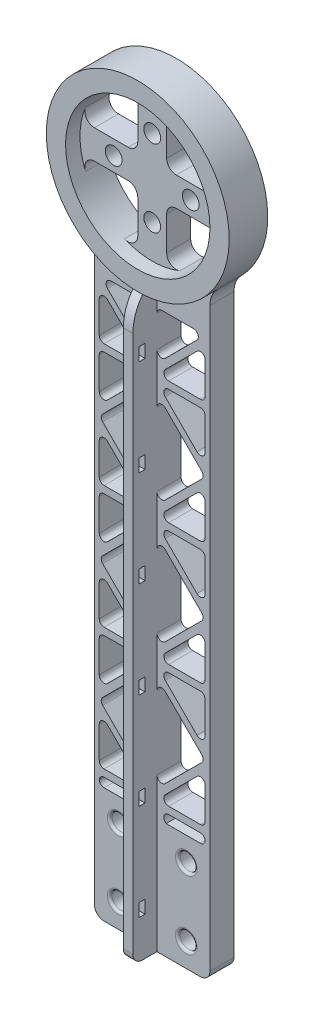
SolidWorks part; units mm, degrees
material "ABS"
ref_plane "Front Plane" through (0, 0, 0) normal (0, 0, 1) x (1, 0, 0)
ref_plane "Top Plane" through (0, 0, 0) normal (0, 1, 0) x (1, 0, 0)
ref_plane "Right Plane" through (0, 0, 0) normal (1, 0, 0) x (0, 0, -1)
sketch "Sketch2" plane through (0, 0, 0) normal (0, 0, 1) x (1, 0, 0)
  line L0 (0, 15) -> (0, -15) construction
  line L1 (-15, 0) -> (15, 0) construction
  line L2 (-3, 14.6969) -> (-3, 3)
  line L3 (-3, 3) -> (-14.6969, 3)
  line L4 (-14.6969, -3) -> (-3, -3)
  line L5 (-3, -3) -> (-3, -14.6969)
  line L6 (3, 14.6969) -> (3, 3)
  line L7 (3, 3) -> (14.6969, 3)
  line L8 (3, -14.6969) -> (3, -3)
  line L9 (3, -3) -> (14.6969, -3)
  line L10 (-12, -14.7309) -> (-12, -114.7309)
  line L11 (12, -14.7309) -> (12, -114.7309)
  line L12 (12, -114.7309) -> (-12, -114.7309)
  circle A0 centre (0, 0) radius 19
  circle A1 centre (0, 0) radius 15
  arc A2 (3, -14.6969) -> (14.6969, -3) centre (0, 0) ccw
  arc A3 (3, 14.6969) -> (14.6969, 3) centre (0, 0) cw
  arc A4 (-14.6969, 3) -> (-3, 14.6969) centre (0, 0) cw
  arc A5 (-14.6969, -3) -> (-3, -14.6969) centre (0, 0) ccw
  arc A6 (-12, -14.7309) -> (12, -14.7309) centre (0, 0) ccw
  dimension "D1" = 30
  dimension "D2" = 4
  dimension "D3" = 3
  dimension "D4" = 3
  dimension "D5" = 3
  dimension "D6" = 3
  dimension "D7" = 3
  dimension "D8" = 3
  dimension "D9" = 3
  dimension "D10" = 3
  dimension "D11" = 3
  dimension "D12" = 3
  dimension "D13" = 100
extrude "Boss-Extrude2" add sketch "Sketch2" along normal blind 8 contours A0 A1 L5 region at (-7.9241, 16.6756, 0)
extrude "Boss-Extrude3" add sketch "Sketch2<6>" along normal blind 5 contours L6 A1 L2 L3 L4 L5 L8 L9 L7 region at (0, 0, 0)
sketch "Sketch2<6>" plane through (0, 0, 0) normal (0, 0, 1) x (1, 0, 0) same geometry as "Sketch2"
fillet "Fillet1" radius 2 12 edges at (-3, 3, 2.5) (3, 3, 2.5) (3, -3, 2.5) (-3, -3, 2.5) (-3, -14.6969, 2.5) (3, -14.6969, 2.5) (14.6969, -3, 2.5) (14.6969, 3, 2.5) (3, 14.6969, 2.5) (-3, 14.6969, 2.5) (-14.6969, -3, 2.5) (-14.6969, 3, 2.5)
sketch "Sketch6" plane through (0, 0, 0) normal (0, 0, 1) x (1, 0, 0)
  line L0 (0, 0) -> (0, 8.3) construction
  line L1 (0, 0) -> (0, -8.3) construction
  line L2 (0, 0) -> (8.35, 0) construction
  line L3 (0, 0) -> (-8.35, 0) construction
  circle A0 centre (8, 0) radius 1.75
  circle A1 centre (0, 8) radius 1.75
  circle A2 centre (-8, 0) radius 1.75
  circle A3 centre (0, -8) radius 1.75
  dimension "D1" = 3.5
  dimension "D2" = 8
  dimension "D3" = 8
  dimension "D4" = 8
  dimension "D5" = 8
extrude "Cut-Extrude2" cut sketch "Sketch6" along normal up to surface (5 mm away) up to face at (0, 0, 5)
extrude "Boss-Extrude4" add sketch "Sketch2<9>" along normal up to surface (5 mm away) contours A0 L10 L12 L11 region at (0, -66.1813, 0) up to face at (9.75, 0, 5)
sketch "Sketch2<9>" plane through (0, 0, 0) normal (0, 0, 1) x (1, 0, 0) same geometry as "Sketch2"
fillet "Fillet2" radius 5 2 edges at (12, -14.7309, 2.5) (-12, -14.7309, 2.5)
sketch "Sketch9" plane through (0, 0, 5) normal (0, 0, 1) x (1, 0, 0)
  line L0 (0, -19) -> (0, -114.7309) construction
  line L1 (12, -114.7309) -> (-12, -114.7309) construction
  line L2 (-11, -203.3442) -> (-11, -213.3442)
  line L3 (-11, -213.3442) -> (-1, -213.3442)
  line L4 (-1, -213.3442) -> (-11, -203.3442)
  line L5 (-11, -201.3442) -> (-1, -211.3442)
  line L6 (-1, -211.3442) -> (-1, -191.3442)
  line L7 (-1, -201.3442) -> (-11, -201.3442)
  line L8 (-11, -189.3442) -> (-1, -189.3442)
  line L9 (-11, -199.3442) -> (-11, -189.3442)
  line L10 (-1, -189.3442) -> (-11, -199.3442)
  line L11 (-11, -201.3442) -> (-1, -191.3442)
  line L12 (-11, -163.8442) -> (-1, -163.8442)
  line L13 (-1, -163.8442) -> (-11, -173.8442)
  line L14 (-11, -173.8442) -> (-11, -163.8442)
  line L15 (-11, -175.8442) -> (-1, -185.8442)
  line L16 (-1, -185.8442) -> (-1, -165.8442)
  line L17 (-11, -175.8442) -> (-1, -165.8442)
  line L18 (-1, -187.8442) -> (-11, -177.8442)
  line L19 (-11, -177.8442) -> (-11, -187.8442)
  line L20 (-11, -187.8442) -> (-1, -187.8442)
  line L21 (-11, -138.3442) -> (-1, -138.3442)
  line L22 (-1, -138.3442) -> (-11, -148.3442)
  line L23 (-11, -148.3442) -> (-11, -138.3442)
  line L24 (-11, -150.3442) -> (-1, -160.3442)
  line L25 (-1, -160.3442) -> (-1, -140.3442)
  line L26 (-11, -150.3442) -> (-1, -140.3442)
  line L27 (-1, -162.3442) -> (-11, -152.3442)
  line L28 (-11, -152.3442) -> (-11, -162.3442)
  line L29 (-11, -162.3442) -> (-1, -162.3442)
  line L30 (-11, -112.8442) -> (-1, -112.8442)
  line L31 (-1, -112.8442) -> (-11, -122.8442)
  line L32 (-11, -122.8442) -> (-11, -112.8442)
  line L33 (-11, -124.8442) -> (-1, -134.8442)
  line L34 (-1, -134.8442) -> (-1, -114.8442)
  line L35 (-11, -124.8442) -> (-1, -114.8442)
  line L36 (-1, -136.8442) -> (-11, -126.8442)
  line L37 (-11, -126.8442) -> (-11, -136.8442)
  line L38 (-11, -136.8442) -> (-1, -136.8442)
  line L39 (-11, -87.3442) -> (-1, -87.3442)
  line L40 (-1, -87.3442) -> (-11, -97.3442)
  line L41 (-11, -97.3442) -> (-11, -87.3442)
  line L42 (-11, -99.3442) -> (-1, -109.3442)
  line L43 (-1, -109.3442) -> (-1, -89.3442)
  line L44 (-11, -99.3442) -> (-1, -89.3442)
  line L45 (-1, -111.3442) -> (-11, -101.3442)
  line L46 (-11, -101.3442) -> (-11, -111.3442)
  line L47 (-11, -111.3442) -> (-1, -111.3442)
  line L48 (-11, -61.8442) -> (-1, -61.8442)
  line L49 (-1, -61.8442) -> (-11, -71.8442)
  line L50 (-11, -71.8442) -> (-11, -61.8442)
  line L51 (-11, -73.8442) -> (-1, -83.8442)
  line L52 (-1, -83.8442) -> (-1, -63.8442)
  line L53 (-11, -73.8442) -> (-1, -63.8442)
  line L54 (-1, -85.8442) -> (-11, -75.8442)
  line L55 (-11, -75.8442) -> (-11, -85.8442)
  line L56 (-11, -85.8442) -> (-1, -85.8442)
  line L57 (-11, -36.3442) -> (-1, -36.3442)
  line L58 (-1, -36.3442) -> (-11, -46.3442)
  line L59 (-11, -46.3442) -> (-11, -36.3442)
  line L60 (-11, -48.3442) -> (-1, -58.3442)
  line L61 (-1, -58.3442) -> (-1, -38.3442)
  line L62 (-11, -48.3442) -> (-1, -38.3442)
  line L63 (-1, -60.3442) -> (-11, -50.3442)
  line L64 (-11, -50.3442) -> (-11, -60.3442)
  line L65 (-11, -60.3442) -> (-1, -60.3442)
  line L69 (-11, -22.8442) -> (-1, -32.8442)
  line L70 (-1, -32.8442) -> (-1, -22.8442)
  line L72 (-1, -34.8442) -> (-11, -24.8442)
  line L73 (-11, -24.8442) -> (-11, -34.8442)
  line L74 (-11, -34.8442) -> (-1, -34.8442)
  line L75 (11, -22.8442) -> (1, -22.8442)
  line L76 (-11, -22.8442) -> (-1, -22.8442)
  line L77 (1, -32.8442) -> (1, -22.8442)
  line L78 (-1, -10.8442) -> (-11, -20.8442)
  line L79 (-11, -16.8895) -> (-11, -10.8442)
  line L80 (-11, -10.8442) -> (-1, -10.8442)
  line L81 (-11, -22.8442) -> (-2.3104, -14.1546)
  line L82 (11, -22.8442) -> (1, -32.8442)
  line L83 (11, -34.8442) -> (1, -34.8442)
  line L84 (11, -24.8442) -> (11, -34.8442)
  line L85 (1, -34.8442) -> (11, -24.8442)
  line L86 (11, -46.3442) -> (11, -36.3442)
  line L87 (1, -36.3442) -> (11, -46.3442)
  line L88 (11, -36.3442) -> (1, -36.3442)
  line L89 (11, -48.3442) -> (1, -38.3442)
  line L90 (1, -58.3442) -> (1, -38.3442)
  line L91 (11, -48.3442) -> (1, -58.3442)
  line L92 (11, -60.3442) -> (1, -60.3442)
  line L93 (11, -50.3442) -> (11, -60.3442)
  line L94 (1, -60.3442) -> (11, -50.3442)
  line L95 (11, -71.8442) -> (11, -61.8442)
  line L96 (1, -61.8442) -> (11, -71.8442)
  line L97 (11, -61.8442) -> (1, -61.8442)
  line L98 (11, -73.8442) -> (1, -63.8442)
  line L99 (1, -83.8442) -> (1, -63.8442)
  line L100 (11, -73.8442) -> (1, -83.8442)
  line L101 (11, -85.8442) -> (1, -85.8442)
  line L102 (11, -75.8442) -> (11, -85.8442)
  line L103 (1, -85.8442) -> (11, -75.8442)
  line L104 (11, -97.3442) -> (11, -87.3442)
  line L105 (1, -87.3442) -> (11, -97.3442)
  line L106 (11, -87.3442) -> (1, -87.3442)
  line L107 (11, -99.3442) -> (1, -89.3442)
  line L108 (1, -109.3442) -> (1, -89.3442)
  line L109 (11, -99.3442) -> (1, -109.3442)
  line L110 (11, -111.3442) -> (1, -111.3442)
  line L111 (11, -101.3442) -> (11, -111.3442)
  line L112 (1, -111.3442) -> (11, -101.3442)
  line L113 (11, -122.8442) -> (11, -112.8442)
  line L114 (1, -112.8442) -> (11, -122.8442)
  line L115 (11, -112.8442) -> (1, -112.8442)
  line L116 (11, -124.8442) -> (1, -114.8442)
  line L117 (1, -134.8442) -> (1, -114.8442)
  line L118 (11, -124.8442) -> (1, -134.8442)
  line L119 (11, -136.8442) -> (1, -136.8442)
  line L120 (11, -126.8442) -> (11, -136.8442)
  line L121 (1, -136.8442) -> (11, -126.8442)
  line L122 (11, -148.3442) -> (11, -138.3442)
  line L123 (1, -138.3442) -> (11, -148.3442)
  line L124 (11, -138.3442) -> (1, -138.3442)
  line L125 (11, -150.3442) -> (1, -140.3442)
  line L126 (1, -160.3442) -> (1, -140.3442)
  line L127 (11, -150.3442) -> (1, -160.3442)
  line L128 (11, -162.3442) -> (1, -162.3442)
  line L129 (11, -152.3442) -> (11, -162.3442)
  line L130 (1, -162.3442) -> (11, -152.3442)
  line L131 (1, -163.8442) -> (11, -173.8442)
  line L132 (11, -173.8442) -> (11, -163.8442)
  line L133 (11, -163.8442) -> (1, -163.8442)
  line L134 (11, -175.8442) -> (1, -165.8442)
  line L135 (1, -185.8442) -> (1, -165.8442)
  line L136 (11, -175.8442) -> (1, -185.8442)
  line L137 (11, -177.8442) -> (11, -187.8442)
  line L138 (11, -187.8442) -> (1, -187.8442)
  line L139 (1, -187.8442) -> (11, -177.8442)
  line L140 (11, -199.3442) -> (11, -189.3442)
  line L141 (1, -189.3442) -> (11, -199.3442)
  line L142 (11, -189.3442) -> (1, -189.3442)
  line L143 (11, -201.3442) -> (1, -191.3442)
  line L144 (1, -211.3442) -> (1, -191.3442)
  line L145 (11, -201.3442) -> (1, -211.3442)
  line L146 (11, -213.3442) -> (1, -213.3442)
  line L147 (11, -203.3442) -> (11, -213.3442)
  line L148 (1, -213.3442) -> (11, -203.3442)
  arc A0 (-13.4583, -13.4117) -> (13.4583, -13.4117) centre (0, 0) ccw construction
  dimension "D1" = 10
  dimension "D2" = 10
  dimension "D3" = 10
  dimension "D4" = 10
  dimension "D5" = 1
  dimension "D6" = 2
  dimension "D7" = 8
extrude "Cut-Extrude4" cut sketch "Sketch9" against normal up to surface (5 mm away) contours L11 L7 L6 | L6 L7 L5 | L7 L5 L6 | L69 L70 L76 | L72 L73 L74 | L75 L77 L82 | L83 L85 L84 | L57 L58 L59 | L60 L61 L62 | L63 L64 L65 | L86 L88 L87 | L89 L90 L91 | L92 L94 L93 | L48 L49 L50 | L51 L52 L53 | L95 L97 L96 | L98 L99 L100 | L54 L55 L56 | L101 L103 L102 | L39 L40 L41 | L104 L106 L105 | L42 L43 L44 | L107 L108 L109 | L110 L112 L111 | L45 L46 L47 | L30 L31 L32 | L113 L115 L114 | L33 L34 L35 | L116 L117 L118 | L36 L37 L38 | L21 L22 L23 | L119 L121 L120 | L122 L124 L123 | L125 L126 L127 | L24 L25 L26 | L27 L28 L29 | L128 L130 L129 | L131 L132 L133 | L12 L14 L13 | L15 L16 L17 | L134 L135 L136 | L137 L138 L139 | L18 L20 L19 | L8 L10 L9 | L140 L142 L141 | L143 L144 L145 | L146 L148 L147 | L4 L2 L3 region at (-4.3333, -204.6775, 5) region at (-4.3333, -198.0108, 5) up to face at (9.75, 0, 0)
sketch "Sketch10" plane through (0, 0, 0) normal (0, 0, 1) x (1, 0, 0)
  line L1 (-12, -114.7309) -> (12, -114.7309)
  line L2 (-12, -114.7309) -> (-12, -138.7309)
  line L3 (-12, -138.7309) -> (12, -138.7309)
  line L4 (12, -114.7309) -> (12, -138.7309)
  dimension "D1" = 24
extrude "Boss-Extrude5" add sketch "Sketch10" along normal up to surface (5 mm away) up to face at (-7.6667, -82.5108, 5)
fillet "Fillet12" radius 2 2 edges at (-12, -138.7309, 2.5) (12, -138.7309, 2.5)
sketch "Sketch11" plane through (0, 0, 0) normal (0, 0, 1) x (1, 0, 0)
  line L0 (11.4142, -138.1451) -> (-12, -114.7309) construction
  line L1 (-12, -16.9411) -> (-12, -136.7309) construction
  line L2 (-12, -114.7309) -> (12, -114.7309) construction
  line L3 (12, -16.9411) -> (12, -136.7309) construction
  line L4 (12, -114.7309) -> (-11.4142, -138.1451) construction
  arc A0 (10, -138.7309) -> (12, -136.7309) centre (10, -136.7309) ccw construction
  arc A1 (-12, -136.7309) -> (-10, -138.7309) centre (-10, -136.7309) ccw construction
  circle A2 centre (-7.0711, -119.6599) radius 1.75
  circle A3 centre (7.0711, -119.6599) radius 1.75
  circle A4 centre (-7.0711, -133.802) radius 1.75
  circle A5 centre (7.0711, -133.802) radius 1.75
  dimension "D1" = 3.5
  dimension "D2" = 10
  dimension "D3" = 10
  dimension "D4" = 10
  dimension "D5" = 10
extrude "Cut-Extrude7" cut sketch "Sketch11" along normal up to surface (5 mm away) up to face at (-6.4717, -113.7875, 5)
fillet "Fillet19" [suppressed] radius 5
sketch "Sketch12" plane through (0, 0, 5) normal (0, 0, 1) x (1, 0, 0)
  line L0 (-1, -102.1184) -> (-1, -138.7309)
  line L1 (-1, -109.3442) -> (-1, -89.3442) construction
  line L2 (-10, -138.7309) -> (10, -138.7309) construction
  line L3 (1, -105.2481) -> (1, -138.7309)
  line L4 (1, -109.3442) -> (1, -89.3442) construction
  line L5 (-1, -102.1184) -> (-1, -18.9737)
  line L6 (1, -26.08) -> (1, -18.9737)
  line L7 (1, -32.8442) -> (1, -22.8442) construction
  line L8 (1, -26.08) -> (1, -105.2481)
  line L9 (-1, -138.7309) -> (1, -138.7309)
  circle A0 centre (0, 0) radius 19 construction
  arc A1 (-1, -18.9737) -> (1, -18.9737) centre (0, 0) ccw
extrude "Boss-Extrude6" add sketch "Sketch12" along normal blind 5
fillet "Fillet20" radius 2 1 edges at (0, -138.7309, 10)
fillet "Fillet21" radius 10 1 edges at (0, -19, 10)
fillet "Fillet23" radius 1 72 edges at (1, -112.8442, 2.5) (-1, -112.8442, 2.5) (-11, -22.8442, 2.5) (-1, -22.8442, 2.5) (-1, -32.8442, 2.5) (-11, -24.8442, 2.5) (-11, -34.8442, 2.5) (-1, -34.8442, 2.5) (1, -22.8442, 2.5) (1, -32.8442, 2.5) (11, -22.8442, 2.5) (11, -24.8442, 2.5) (11, -34.8442, 2.5) (1, -34.8442, 2.5) (1, -36.3442, 2.5) (11, -46.3442, 2.5) (11, -36.3442, 2.5) (-1, -36.3442, 2.5) (-11, -46.3442, 2.5) (-11, -36.3442, 2.5) (-11, -48.3442, 2.5) (-1, -38.3442, 2.5) (-1, -58.3442, 2.5) (1, -58.3442, 2.5) (11, -48.3442, 2.5) (11, -50.3442, 2.5) (1, -60.3442, 2.5) (11, -60.3442, 2.5) (1, -61.8442, 2.5) (11, -71.8442, 2.5) (11, -61.8442, 2.5) (-1, -63.8442, 2.5) (-11, -73.8442, 2.5) (-1, -83.8442, 2.5) (1, -83.8442, 2.5) (11, -73.8442, 2.5) (11, -75.8442, 2.5) (1, -85.8442, 2.5) (1, -87.3442, 2.5) (11, -97.3442, 2.5) (11, -85.8442, 2.5) (-1, -85.8442, 2.5) (-11, -85.8442, 2.5) (-1, -87.3442, 2.5) (-11, -97.3442, 2.5) (1, -38.3442, 2.5) (1, -63.8442, 2.5) (-11, -50.3442, 2.5) (-11, -61.8442, 2.5) (-11, -87.3442, 2.5) (-11, -75.8442, 2.5) (11, -87.3442, 2.5) (-1, -89.3442, 2.5) (1, -89.3442, 2.5) (-1, -109.3442, 2.5) (1, -109.3442, 2.5) (-11, -99.3442, 2.5) (11, -99.3442, 2.5) (11, -111.3442, 2.5) (1, -111.3442, 2.5) (11, -101.3442, 2.5) (-11, -101.3442, 2.5) (-11, -111.3442, 2.5) (-1, -111.3442, 2.5) (-11, -112.8442, 2.5) (11, -112.8442, 2.5) (11, -114.7309, 2.5) (-11, -114.7309, 2.5) (-1, -61.8442, 2.5) (-1, -60.3442, 2.5) (-11, -60.3442, 2.5) (-11, -71.8442, 2.5)
sketch "Sketch13" plane through (1, 0, 0) normal (1, 0, 0) x (0, 0, -1)
  line L0 (-10, -136.7309) -> (-10, -24.98) construction
  line L1 (-7.5, -130.7309) -> (-8.75, -130.7309)
  line L2 (-7.5, -130.7309) -> (-7.5, -128.0309)
  line L3 (-7.5, -128.0309) -> (-8.75, -128.0309)
  line L4 (-8.75, -130.7309) -> (-8.75, -128.0309)
  line L5 (-8, -138.7309) -> (-5, -138.7309) construction
  dimension "D1" = 2.7
  dimension "D2" = 1.25
  dimension "D3" = 1.25
  dimension "D4" = 8
extrude "Cut-Extrude8" cut sketch "Sketch13" against normal up to surface (2 mm away) up to face at (-1, -68.7551, 4.2283)
pattern_linear "LPattern1" count 6 spacing 20 along (0, 1, 0) of "Cut-Extrude8"
fillet "Fillet24" radius 0.5 4 edges at (8.8211, -133.802, 5) (-5.3211, -133.802, 5) (8.8211, -119.6599, 5) (-5.3211, -119.6599, 5)
